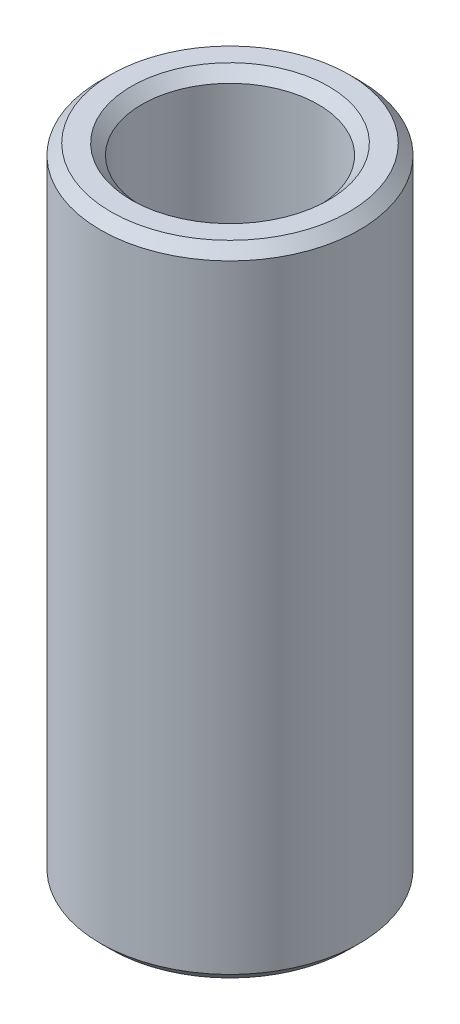
SolidWorks part; units mm, degrees
ref_plane "Front Plane" through (0, 0, 0) normal (0, 0, 1) x (1, 0, 0)
ref_plane "Top Plane" through (0, 0, 0) normal (0, 1, 0) x (1, 0, 0)
ref_plane "Right Plane" through (0, 0, 0) normal (1, 0, 0) x (0, 0, -1)
sketch "Sketch1" plane through (0, 0, 0) normal (0, 1, 0) x (1, 0, 0)
  circle A0 centre (0, 0) radius 30
  dimension "SLEEVE_OD" = 60
extrude "Boss-Extrude1" add sketch "Sketch1" along normal blind 148.0316
sketch "Sketch2" plane through (0, 0, 0) normal (0, 1, 0) x (1, 0, 0)
  circle A0 centre (0, 0) radius 20.4215
  dimension "BORE_D" = 40.843
extrude "Cut-Extrude1" cut sketch "Sketch2" along normal through all
chamfer "Chamfer1" distance 2.4227 angle 45 4 edges at (0, 148.0316, 20.4215) (0, 0, 20.4215) (0, 0, 30) (0, 148.0316, 30)
